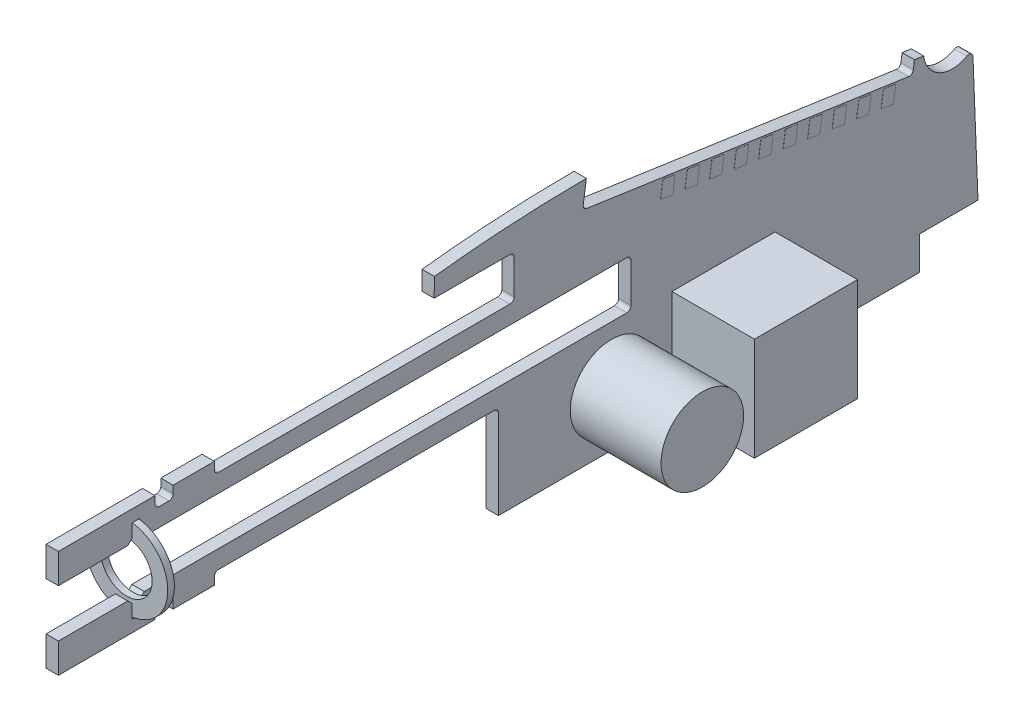
SolidWorks part; units mm, degrees
ref_plane "Спереди" through (0, 0, 0) normal (0, 0, 1) x (1, 0, 0)
ref_plane "Сверху" through (0, 0, 0) normal (0, 1, 0) x (1, 0, 0)
ref_plane "Справа" through (0, 0, 0) normal (1, 0, 0) x (0, 0, -1)
other "Configuration Table"
sketch "Sketch1" plane through (0, 0, 0) normal (1, 0, 0) x (0, 0, -1)
  line L5 (37.45, -2.4369) -> (37.45, 2.3631)
  line L8 (-20.2, 6.4631) -> (-20.2, 5.5631)
  line L9 (-31.9035, 2.8631) -> (-31.9035, 6.4631)
  line L11 (-19.7, 5.0631) -> (-18.5, 5.0631)
  line L12 (-19.7, -5.1369) -> (-18.5, -5.1369)
  line L13 (-20.2, -6.5369) -> (-31.9035, -6.5369)
  line L14 (-31.9035, -6.5369) -> (-31.9035, -2.9369)
  line L15 (-31.9035, 6.4631) -> (-20.2, 6.4631)
  line L16 (36.95, -2.9369) -> (-21.5, -2.9369)
  line L17 (-20.2, -5.6369) -> (-20.2, -6.5369)
  line L19 (36.95, 2.8631) -> (-21.5, 2.8631)
  line L24 (79.4958, -12.3913) -> (78.8893, 2.9846)
  line L26 (13.6527, 12.5347) -> (13.6131, 10.2638)
  line L27 (32.0989, 10.4462) -> (71.0896, 4.7823)
  line L28 (-23, 4.9936) -> (-23, 3.3631)
  line L30 (79.4958, -12.3913) -> (72.3831, -12.3913)
  line L35 (13.6131, 10.2638) -> (22.8087, 10.2638)
  line L37 (23.3087, 5.5631) -> (23.3087, 9.7638)
  line L40 (-23, -5.0933) -> (-22, -5.0933)
  line L41 (-22, -5.0933) -> (-22, -3.4369)
  line L42 (-22, 4.9936) -> (-23, 4.9936)
  line L43 (-23, -3.4369) -> (-23, -5.0933)
  line L44 (-22, 3.3631) -> (-22, 4.9936)
  line L45 (-23.5, 2.8631) -> (-31.9035, 2.8631)
  line L46 (-23.5, -2.9369) -> (-31.9035, -2.9369)
  line L47 (-23, 3.3631) -> (-23.5, 2.8631)
  line L48 (-21.5, 2.8631) -> (-22, 3.3631)
  line L49 (-22, -3.4369) -> (-21.5, -2.9369)
  line L50 (-23.5, -2.9369) -> (-23, -3.4369)
  line L52 (-13, 6.4631) -> (-13, 5.5631)
  line L55 (-13, -5.6369) -> (-13, -6.5369)
  line L56 (-18, 6.4631) -> (-13, 6.4631)
  line L57 (-18, 6.4631) -> (-18, 5.5631)
  line L58 (-12.5, -5.1369) -> (20.8965, -5.1369)
  line L59 (-12.5, 5.0631) -> (22.8087, 5.0631)
  line L60 (-18, -5.6369) -> (-18, -6.5369)
  line L61 (-18, -6.5369) -> (-13, -6.5369)
  line L64 (71.8001, 6.1949) -> (72.9223, 6.0319)
  line L67 (71.8001, 6.1949) -> (71.6563, 5.2053)
  line L68 (32.0549, 13.6217) -> (31.6759, 11.0129)
  line L71 (72.3831, -16.4336) -> (72.3831, -12.3913)
  line L73 (72.3831, -16.4336) -> (63.1965, -16.4336)
  line L74 (56.1965, -15.8336) -> (56.1965, -16.4336)
  line L75 (63.1965, -15.8336) -> (63.1965, -16.4336)
  line L76 (56.1965, -16.4336) -> (21.3965, -16.4336)
  line L78 (21.3965, -5.6369) -> (21.3965, -16.4336)
  arc A0 (72.9223, 6.0319) -> (78.1408, 3.3986) centre (76.3991, 6.4344) ccw
  arc A1 (78.1408, 3.3986) -> (78.8893, 2.9846) centre (78.3896, 2.9649) cw
  arc A2 (71.6563, 5.2053) -> (71.0896, 4.7823) centre (71.1615, 5.2771) cw
  arc A3 (31.6759, 11.0129) -> (32.0989, 10.4462) centre (32.1707, 10.941) ccw
  arc A4 (-20.2, 5.5631) -> (-19.7, 5.0631) centre (-19.7, 5.5631) ccw
  arc A5 (-18, 5.5631) -> (-18.5, 5.0631) centre (-18.5, 5.5631) cw
  arc A6 (-13, 5.5631) -> (-12.5, 5.0631) centre (-12.5, 5.5631) ccw
  arc A7 (-13, -5.6369) -> (-12.5, -5.1369) centre (-12.5, -5.6369) cw
  arc A8 (-20.2, -5.6369) -> (-19.7, -5.1369) centre (-19.7, -5.6369) cw
  arc A9 (-18, -5.6369) -> (-18.5, -5.1369) centre (-18.5, -5.6369) ccw
  arc A11 (36.95, -2.9369) -> (37.45, -2.4369) centre (36.95, -2.4369) ccw
  arc A12 (37.45, 2.3631) -> (36.95, 2.8631) centre (36.95, 2.3631) ccw
  arc A13 (22.8087, 5.0631) -> (23.3087, 5.5631) centre (22.8087, 5.5631) ccw
  arc A14 (22.8087, 10.2638) -> (23.3087, 9.7638) centre (22.8087, 9.7638) cw
  arc A17 (63.1965, -15.8336) -> (56.1965, -15.8336) centre (59.6965, -15.8336) ccw
  arc A18 (21.3965, -5.6369) -> (20.8965, -5.1369) centre (20.8965, -5.6369) ccw
  spline S1 degree 3 poles (32.0549, 13.6217) (30.6328, 13.6189) (27.6447, 13.5735) (23.109, 13.3787) (18.3976, 13.0396) (15.2469, 12.7201) (13.6527, 12.5347) knots 0.843998 0.843998 0.843998 0.843998 0.921319 1.006377 1.091434 1.178911 1.178911 1.178911 1.178911
  point P2 (24.3, -5.1)
  point P5 (24.3, 5.1)
  point P7 (24.3, 0)
  point P9 (24.3, 0)
  point P11 (0, 0)
  point P13 (-33.3, 0)
  point P14 (-20.2, -5.0871)
  point P15 (-20.1, -6.0871)
  point P16 (-33.3, 0)
  point P20 (-33.3, 0)
  point P24 (65.5, -6.0871)
  point P26 (-23, 2.9129)
  point P28 (-23, -2.8871)
  point P32 (65.5, -5.0871)
  point P36 (-22, -2.8871)
  point P38 (-22, 2.9129)
  dimension "D1" = 0.5
extrude "Boss-Extrude1" add sketch "Sketch1" along normal blind 0.75 and the other way blind 0.75
sketch "Sketch3" plane through (0, 0, 20.2) normal (0, 0, -1) x (-1, 0, 0)
  circle A0 centre (0, 0) radius 3.1
  circle A3 centre (0, 0) radius 5
  point P7 (0, 0)
extrude "Boss-Extrude2" add sketch "Sketch3" against normal blind 0.8 from offset 1.9 separate body offset against normal yes
sketch "Sketch4" plane through (0.75, 0, 0) normal (1, 0, 0) x (0, 0, -1)
  line L0 (28.8653, 13.3921) -> (28.7426, 18.8834)
  line L1 (22.5184, 13.1214) -> (22.2571, 18.1533)
  line L2 (16.1633, 12.5992) -> (15.6502, 17.6026)
sketch "Sketch5" plane through (0.75, 0, 0) normal (1, 0, 0) x (0, 0, -1)
  line L0 (37.45, -0.0369) -> (-44.232, -0.0369) construction
  line L1 (37.45, 2.3631) -> (37.45, -2.4369) construction
sketch "Sketch6" plane through (0.75, 0, 0) normal (1, 0, 0) x (0, 0, -1)
  line L0 (48.7411, 7.8158) -> (48.4536, 5.8366)
  line L1 (47.2567, 8.0314) -> (46.9692, 6.0522)
  line L2 (42.5159, 6.6991) -> (41.0315, 6.9147)
  line L3 (45.4847, 6.2679) -> (44.0003, 6.4835)
  line L4 (48.4536, 5.8366) -> (46.9692, 6.0522)
  line L5 (48.7411, 7.8158) -> (47.2567, 8.0314)
  line L6 (66.2666, 3.2491) -> (64.7822, 3.4647)
  line L7 (69.2355, 2.8178) -> (67.751, 3.0334)
  line L8 (42.8034, 8.6783) -> (41.319, 8.894)
  line L9 (45.7722, 8.2471) -> (44.2878, 8.4627)
  line L10 (66.5541, 5.2283) -> (65.0697, 5.4439)
  line L11 (69.523, 4.797) -> (68.0385, 5.0127)
  line L12 (41.319, 8.894) -> (41.0315, 6.9147)
  line L13 (42.8034, 8.6783) -> (42.5159, 6.6991)
  line L14 (44.2878, 8.4627) -> (44.0003, 6.4835)
  line L15 (45.7722, 8.2471) -> (45.4847, 6.2679)
  line L16 (65.0697, 5.4439) -> (64.7822, 3.4647)
  line L17 (66.5541, 5.2283) -> (66.2666, 3.2491)
  line L18 (68.0385, 5.0127) -> (67.751, 3.0334)
  line L19 (69.523, 4.797) -> (69.2355, 2.8178)
  line L24 (50.2255, 7.6002) -> (49.938, 5.621)
  line L25 (51.7099, 7.3846) -> (51.4224, 5.4053)
  line L26 (51.4224, 5.4053) -> (49.938, 5.621)
  line L27 (51.7099, 7.3846) -> (50.2255, 7.6002)
  line L28 (53.1943, 7.1689) -> (52.9068, 5.1897)
  line L29 (54.6788, 6.9533) -> (54.3913, 4.9741)
  line L30 (54.3913, 4.9741) -> (52.9068, 5.1897)
  line L31 (54.6788, 6.9533) -> (53.1943, 7.1689)
  line L32 (56.1632, 6.7377) -> (55.8757, 4.7585)
  line L33 (57.6476, 6.5221) -> (57.3601, 4.5428)
  line L34 (57.3601, 4.5428) -> (55.8757, 4.7585)
  line L35 (57.6476, 6.5221) -> (56.1632, 6.7377)
  line L36 (59.132, 6.3064) -> (58.8445, 4.3272)
  line L37 (60.6164, 6.0908) -> (60.3289, 4.1116)
  line L38 (60.3289, 4.1116) -> (58.8445, 4.3272)
  line L39 (60.6164, 6.0908) -> (59.132, 6.3064)
  line L40 (62.1009, 5.8752) -> (61.8134, 3.8959)
  line L41 (63.5853, 5.6595) -> (63.2978, 3.6803)
  line L42 (63.2978, 3.6803) -> (61.8134, 3.8959)
  line L43 (63.5853, 5.6595) -> (62.1009, 5.8752)
  dimension "D1" = 2
extrude "Boss-Extrude3" add sketch "Sketch6" along normal blind 0.01
sketch "Sketch7" plane through (0.75, 0, 0) normal (1, 0, 0) x (0, 0, -1)
  line L0 (42.4131, -15.9196) -> (54.9077, -15.9196)
  line L1 (42.4131, -15.9196) -> (42.4131, -3.425)
  line L2 (54.9077, -15.9196) -> (54.9077, -3.425)
  line L3 (42.4131, -3.425) -> (54.9077, -3.425)
  line L4 (42.4131, -15.9196) -> (54.9077, -3.425) construction
  line L5 (54.9077, -15.9196) -> (42.4131, -3.425) construction
  point P1 (48.6604, -9.6723)
extrude "Boss-Extrude4" add sketch "Sketch7" along normal blind 10
sketch "Sketch8" plane through (0.75, 0, 0) normal (1, 0, 0) x (0, 0, -1)
  circle A0 centre (35.1035, -9.7866) radius 5
extrude "Boss-Extrude5" add sketch "Sketch8" along normal blind 11
